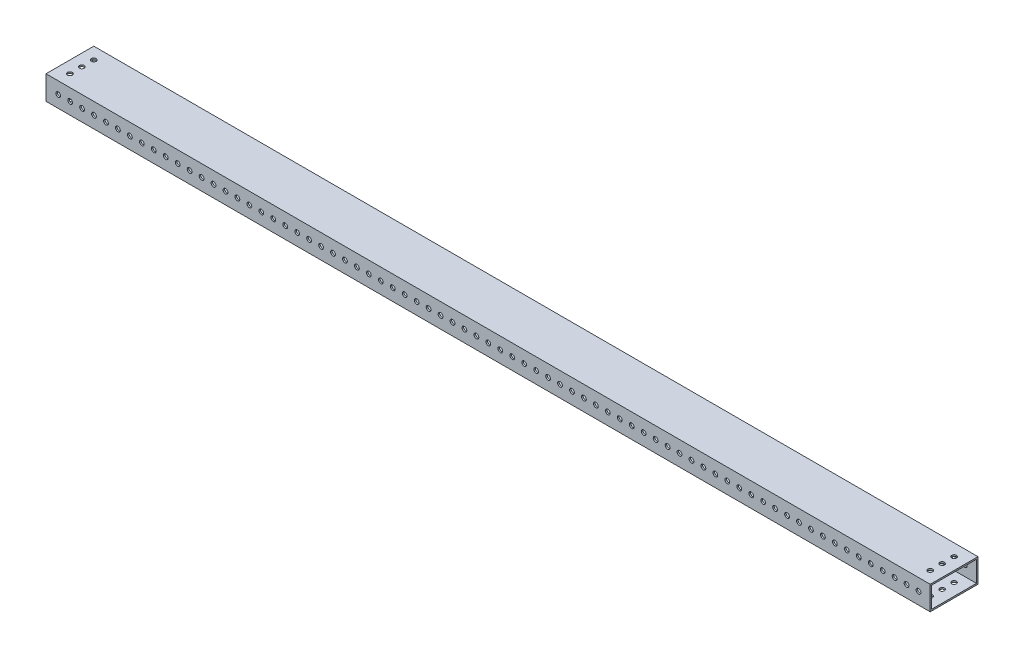
SolidWorks part; units mm, degrees
ref_plane "Front Plane" through (0, 0, 0) normal (0, 0, 1) x (1, 0, 0)
ref_plane "Top Plane" through (0, 0, 0) normal (0, 1, 0) x (1, 0, 0)
ref_plane "Right Plane" through (0, 0, 0) normal (1, 0, 0) x (0, 0, -1)
sketch "Sketch1" plane through (0, 0, 0) normal (0, 1, 0) x (1, 0, 0)
  line L1 (469.9, 25.4) -> (-469.9, 25.4)
  line L2 (469.9, 25.4) -> (469.9, -25.4)
  line L3 (469.9, -25.4) -> (-469.9, -25.4)
  line L4 (-469.9, 25.4) -> (-469.9, -25.4)
  line L5 (469.9, 25.4) -> (-469.9, -25.4) construction
  line L6 (469.9, -25.4) -> (-469.9, 25.4) construction
  point P0 (0, 0)
  dimension "D1" = 50.8
  dimension "D2" = 939.8
extrude "Boss-Extrude1" add sketch "Sketch1" along normal blind 25.4
sketch "Sketch2" plane through (-469.9, 0, 0) normal (-1, 0, 0) x (0, 0, 1)
  line L1 (23.7937, 23.7836) -> (-23.7836, 23.7836)
  line L2 (23.7937, 23.7836) -> (23.7937, 1.6265)
  line L3 (23.7937, 1.6265) -> (-23.7836, 1.6265)
  line L4 (-23.7836, 23.7836) -> (-23.7836, 1.6265)
  line L6 (-25.4, 25.4) -> (-25.4, 0) construction
  line L7 (25.4, 25.4) -> (25.4, 0) construction
  dimension "D1" = 2.286
  dimension "D2" = 2.286
  dimension "D3" = 1.6164
  dimension "D4" = 1.6063
extrude "Cut-Extrude1" cut sketch "Sketch2" against normal through all
sketch "Sketch3" plane through (0, 0, 25.4) normal (0, 0, 1) x (1, 0, 0)
  line L0 (-1393.7901, 12.7) -> (48606.2099, 12.7) construction
  line L1 (-469.9, 25.4) -> (-469.9, 0) construction
  circle A1 centre (-456.946, 12.7) radius 2.54
  circle A2 centre (-444.246, 12.7) radius 2.54
  circle A3 centre (-431.546, 12.7) radius 2.54
  circle A4 centre (-418.846, 12.7) radius 2.54
  circle A5 centre (-406.146, 12.7) radius 2.54
  circle A6 centre (-393.446, 12.7) radius 2.54
  circle A7 centre (-380.746, 12.7) radius 2.54
  circle A8 centre (-368.046, 12.7) radius 2.54
  circle A9 centre (-355.346, 12.7) radius 2.54
  circle A10 centre (-342.646, 12.7) radius 2.54
  circle A11 centre (-329.946, 12.7) radius 2.54
  circle A12 centre (-317.246, 12.7) radius 2.54
  circle A13 centre (-304.546, 12.7) radius 2.54
  circle A14 centre (-291.846, 12.7) radius 2.54
  circle A15 centre (-279.146, 12.7) radius 2.54
  circle A16 centre (-266.446, 12.7) radius 2.54
  circle A17 centre (-253.746, 12.7) radius 2.54
  circle A18 centre (-241.046, 12.7) radius 2.54
  circle A19 centre (-228.346, 12.7) radius 2.54
  circle A20 centre (-215.646, 12.7) radius 2.54
  circle A21 centre (-202.946, 12.7) radius 2.54
  circle A22 centre (-190.246, 12.7) radius 2.54
  circle A23 centre (-177.546, 12.7) radius 2.54
  circle A24 centre (-164.846, 12.7) radius 2.54
  circle A25 centre (-152.146, 12.7) radius 2.54
  circle A26 centre (-139.446, 12.7) radius 2.54
  circle A27 centre (-126.746, 12.7) radius 2.54
  circle A28 centre (-114.046, 12.7) radius 2.54
  circle A29 centre (-101.346, 12.7) radius 2.54
  circle A30 centre (-88.646, 12.7) radius 2.54
  circle A31 centre (-75.946, 12.7) radius 2.54
  circle A32 centre (-63.246, 12.7) radius 2.54
  circle A33 centre (-50.546, 12.7) radius 2.54
  circle A34 centre (-37.846, 12.7) radius 2.54
  circle A35 centre (-25.146, 12.7) radius 2.54
  circle A36 centre (-12.446, 12.7) radius 2.54
  circle A37 centre (0.254, 12.7) radius 2.54
  circle A38 centre (12.954, 12.7) radius 2.54
  circle A39 centre (25.654, 12.7) radius 2.54
  circle A40 centre (38.354, 12.7) radius 2.54
  circle A41 centre (51.054, 12.7) radius 2.54
  circle A42 centre (63.754, 12.7) radius 2.54
  circle A43 centre (76.454, 12.7) radius 2.54
  circle A44 centre (89.154, 12.7) radius 2.54
  circle A45 centre (101.854, 12.7) radius 2.54
  circle A46 centre (114.554, 12.7) radius 2.54
  circle A47 centre (127.254, 12.7) radius 2.54
  circle A48 centre (139.954, 12.7) radius 2.54
  circle A49 centre (152.654, 12.7) radius 2.54
  circle A50 centre (165.354, 12.7) radius 2.54
  circle A51 centre (178.054, 12.7) radius 2.54
  circle A52 centre (190.754, 12.7) radius 2.54
  circle A53 centre (203.454, 12.7) radius 2.54
  circle A54 centre (216.154, 12.7) radius 2.54
  circle A55 centre (228.854, 12.7) radius 2.54
  circle A56 centre (241.554, 12.7) radius 2.54
  circle A57 centre (254.254, 12.7) radius 2.54
  circle A58 centre (266.954, 12.7) radius 2.54
  circle A59 centre (279.654, 12.7) radius 2.54
  circle A60 centre (292.354, 12.7) radius 2.54
  circle A61 centre (305.054, 12.7) radius 2.54
  circle A62 centre (317.754, 12.7) radius 2.54
  circle A63 centre (330.454, 12.7) radius 2.54
  circle A64 centre (343.154, 12.7) radius 2.54
  circle A65 centre (355.854, 12.7) radius 2.54
  circle A66 centre (368.554, 12.7) radius 2.54
  circle A67 centre (381.254, 12.7) radius 2.54
  circle A68 centre (393.954, 12.7) radius 2.54
  circle A69 centre (406.654, 12.7) radius 2.54
  circle A70 centre (419.354, 12.7) radius 2.54
  circle A71 centre (432.054, 12.7) radius 2.54
  circle A72 centre (444.754, 12.7) radius 2.54
  circle A73 centre (457.454, 12.7) radius 2.54
  point P5 (-469.9, 12.7)
  dimension "D1" = 5.08
  dimension "D2" = 12.954
  dimension "D4" = 12.7
  dimension "D6" = 12.7
  dimension "D3" = 60
  dimension "D5" = 14
extrude "Cut-Extrude2" cut sketch "Sketch3" against normal through all
sketch "Sketch4" plane through (0, 25.4, 0) normal (0, 1, 0) x (1, 0, 0)
  line L0 (-1393.7901, 0) -> (48606.2099, 0) construction
  line L1 (-469.9, 25.4) -> (-469.9, -25.4) construction
  line L2 (-1388.247, 12.7) -> (48611.753, 12.7) construction
  line L3 (-1379.4121, -12.7) -> (48620.5879, -12.7) construction
  line L4 (-469.9, -25.4) -> (469.9, -25.4) construction
  line L5 (0, 25.4) -> (0, -25.4) construction
  line L6 (469.9, 25.4) -> (-469.9, 25.4) construction
  circle A0 centre (-457.2, 12.7) radius 2.54
  circle A2 centre (-457.2, -12.7) radius 2.54
  circle A3 centre (-457.2, 0) radius 2.54
  circle A4 centre (457.2, 12.7) radius 2.54
  circle A5 centre (457.2, 0) radius 2.54
  circle A6 centre (457.2, -12.7) radius 2.54
  point P5 (-469.9, 0)
  dimension "D1" = 5.08
  dimension "D5" = 12.7
  dimension "D6" = 5.08
  dimension "D2" = 12.7
  dimension "D3" = 12.7
  dimension "D4" = 12.7
extrude "Cut-Extrude3" cut sketch "Sketch4" against normal through all
